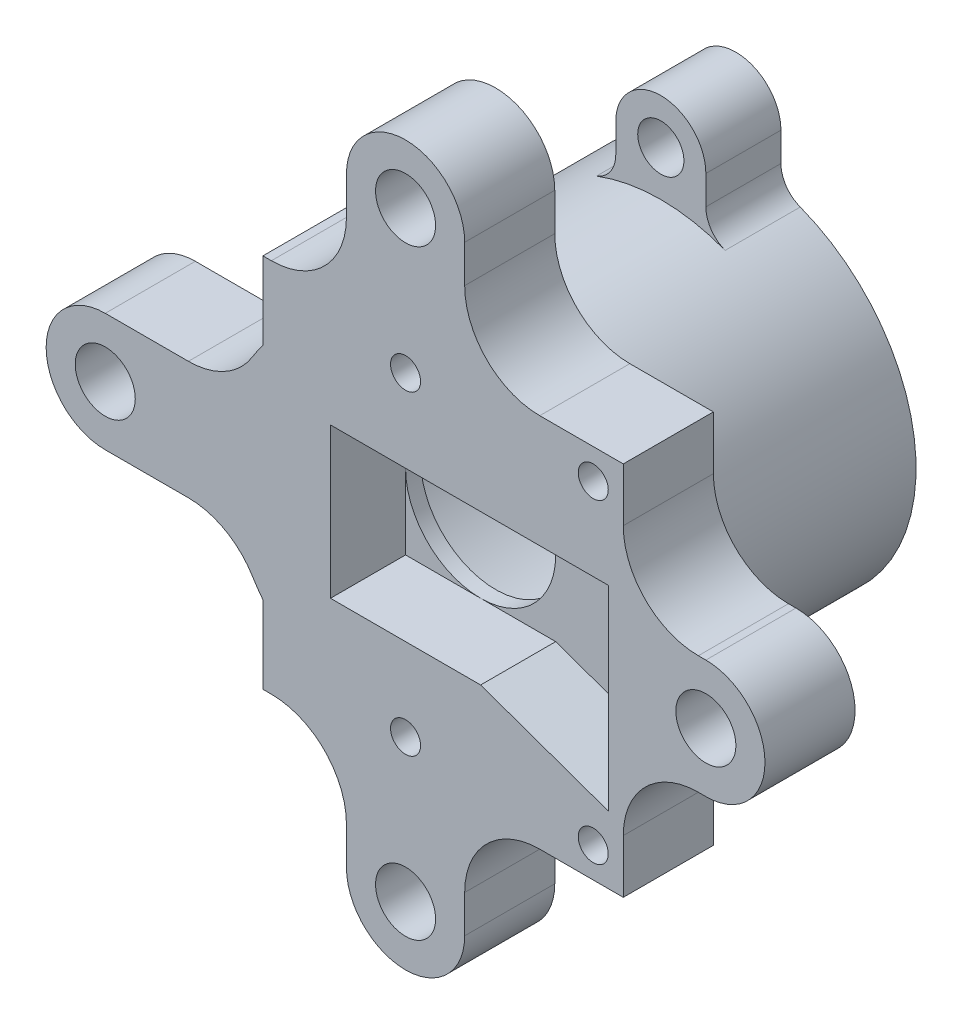
SolidWorks part; units mm, degrees
ref_plane "Front Plane" through (0, 0, 0) normal (1, 0, 0) x (0, 1, 0)
ref_plane "Top Plane" through (0, 0, 0) normal (0, 0, 1) x (0, 1, 0)
ref_plane "Right Plane" through (0, 0, 0) normal (0, 1, 0) x (-1, 0, 0)
sketch "Sketch1" plane through (0, 0, 0) normal (0, 0, 1) x (0, 1, 0)
  circle A0 centre (0, 0) radius 4.75
  circle A2 centre (0, 0) radius 12
extrude "Boss-Extrude1" add sketch "Sketch1" against normal blind 2 contours A2 | A2 A0 | A2 | A2 | A2 | A2 region at (0, -11.6606, 0)
sketch "Sketch2" plane through (0, 0, -2) normal (0, 0, -1) x (1, 0, 0)
  circle A0 centre (0, 0) radius 12
  circle A1 centre (0, 0) radius 10.8716
extrude "Boss-Extrude3" add sketch "Sketch2" along normal blind 20
sketch "Sketch3" plane through (0, 0, -22) normal (0, 0, -1) x (1, 0, 0)
  line L0 (0, 0) -> (0, 15)
  line L1 (-3, 15) -> (-3, 11.619)
  line L2 (3, 15) -> (3, 11.619)
  line L3 (0, 0) -> (3, 0)
  line L4 (-3, -15) -> (-3, -11.619)
  line L5 (3, -15) -> (3, -11.619)
  circle A0 centre (0, 0) radius 12
  circle A1 centre (0, 15) radius 3
  circle A2 centre (0, 15) radius 1.5391
  circle A3 centre (0, -15) radius 3
  circle A4 centre (0, -15) radius 1.5391
  circle M7 centre (0, 0) radius 12
extrude "Boss-Extrude4" add sketch "Sketch3" against normal blind 5 contours A1 L1 M7 | A1 L2 M7 | A2 A1 | L4 A3 M7 | A0 A3 L5 | A3 A4 region at (2.3172, -12.5416, -22) region at (-2.3172, -12.5416, -22) region at (-2.0613, -12.9387, -22) region at (-2.3172, 12.5416, -22) region at (2.3172, 12.5416, -22) region at (-2.0613, 12.9387, -22)
sketch "Sketch5" plane through (0, 0, 0) normal (0, 0, 1) x (1, 0, 0)
  line L0 (0, 0) -> (14.5, 0)
  line L1 (0, 0) -> (0, 10.5)
  line L2 (14.5, 0) -> (-9.5, 0)
  line L3 (14.5, -12.5) -> (14.5, 12.5)
  line L4 (14.5, 12.5) -> (-9.5, 12.5)
  line L5 (-9.5, -12.5) -> (-9.5, 12.5)
  line L6 (0, 10.5) -> (12.5, 10.5)
  line L7 (14.5, -12.5) -> (-9.5, -12.5)
  line L8 (13.5, -5) -> (13.5, -8.0225)
  line L9 (-5, -5) -> (5, -5)
  line L10 (-5, -5) -> (-5, 5)
  line L11 (-5, 5) -> (5, 5)
  line L12 (5, -5) -> (5, 5)
  line L13 (-5, -5) -> (5, 5) construction
  line L14 (-5, 5) -> (5, -5) construction
  line L15 (5, 5) -> (13.5, 5)
  line L16 (5, 5) -> (5, -5)
  line L17 (5, -5) -> (13.5, -5)
  line L18 (13.5, 5) -> (13.5, -5)
  line L19 (13.5, -8.0225) -> (5, -5)
  circle A0 centre (0, 10.5) radius 1
  circle A1 centre (12.5, 10.5) radius 1
  circle A2 centre (0, -10.5) radius 1
  circle A3 centre (12.5, -10.5) radius 1
  circle A4 centre (0, 0) radius 12
  circle M12 centre (0, 0) radius 4.75
  circle M13 centre (0, 0) radius 12
  dimension "D4" = 10
  dimension "D1" = 14.5
  dimension "D2" = 24
  dimension "D3" = 12.5
  dimension "D5" = 10
  dimension "D6" = 8.5
extrude "Boss-Extrude5" add sketch "Sketch5" against normal blind 5 contours A0 L1 L11 L15 L6 M13 | A1 L15 L18 L2 L3 L4 L5 M13 | A0 L6 L5 L2 L10 L11 L1 M13 | L19 L9 L10 L2 L5 A2 M13 | L8 L19 L5 L7 L3 L2 L18 A3 M13 | L5 M13 region at (-4.6617, 6.5575, 0) region at (4.6373, 7.4557, 0) region at (-1.5594, -6.9537, 0) region at (-10.5095, 0, 0) region at (13.7706, 2.5, 0) region at (14, -0.2706, 0)
extrude "Cut-Extrude4" cut sketch "Sketch5<4>" against normal blind 5 contours L11 L10 L2 L1 M12 | L0 L12 L11 L1 M12 | L9 L12 L0 L2 L10 M12 | L6 A0 L1 | L1 A0 L6 | A2 | L12 L17 L2 M13 | L15 L12 L2 M13 | L19 L17 M13 region at (3.6783, 3.6783, 0) region at (4.875, -0.1118, 0) region at (-3.6783, 3.6783, 0) region at (8.3294, 2.4322, 0) region at (8.3294, -2.4322, 0) region at (8.6297, -5.5866, 0) region at (-0.1415, 10.6415, 0) region at (0.4244, 10.0756, 0) region at (0, -10.5, 0)
sketch "Sketch5<4>" plane through (0, 0, 0) normal (0, 0, 1) x (1, 0, 0) same geometry as "Sketch5"
sketch "Sketch6" plane through (0, 0, -5) normal (0, 0, -1) x (1, 0, 0)
  line L0 (14.5, 12.5) -> (14.5, -12.5) construction
  line L1 (-9.5, 12.5) -> (14.5, 12.5)
  line L2 (-9.5, 12.5) -> (-9.5, -12.5)
  line L3 (-9.5, -12.5) -> (14.5, -12.5)
  line L4 (14.5, 12.5) -> (14.5, -12.5)
  circle A0 centre (0, 0) radius 12
  circle M1 centre (12.5, 10.5) radius 1
  circle M2 centre (12.5, -10.5) radius 1
  arc M3 (-9.5, 7.3314) -> (9.9215, 6.75) centre (0, 0) cw
  line M4 (9.9215, 6.75) -> (13.5, 8.0225)
  line M5 (13.5, 8.0225) -> (13.5, -5)
  line M6 (13.5, -5) -> (10.9087, -5)
  arc M7 (10.9087, -5) -> (-9.5, -7.3314) centre (0, 0) cw
  line M8 (-9.5, -7.3314) -> (-9.5, -12.5)
  line M9 (-9.5, -12.5) -> (14.5, -12.5)
  line M10 (14.5, -12.5) -> (14.5, 12.5)
  line M11 (14.5, 12.5) -> (-9.5, 12.5)
  line M12 (-9.5, 12.5) -> (-9.5, 7.3314)
extrude "Boss-Extrude11" add sketch "Sketch6" along normal blind 1 contours M12 M3 M4 M5 M6 M7 M8 M9 M10 M11 M2 M1 | A0 M6 M5 M4 | M1 | M2 region at (2.5, -12.1534, -5) region at (12.404, -1.8318, -5) region at (12.5, -10.5, -5) region at (12.5, 10.5, -5)
combine bodies "Combine1" operation type add bodies to combine 105 108 111
fillet "Fillet2" radius 2 4 edges at (3, 11.619, -19.5) (3, -11.619, -19.5) (-3, 11.619, -19.5) (-3, -11.619, -19.5)
sketch "Sketch7" plane through (0, 0, -5) normal (0, 0, -1) x (1, 0, 0)
  circle A0 centre (0, 0) radius 5
  circle A1 centre (0, 0) radius 12
  arc M1 (0.9438, -10.8306) -> (9.6536, -5) centre (0, 0) ccw
  line M2 (9.6536, -5) -> (-5, -5)
  line M3 (-5, -5) -> (-5, 5)
  line M4 (-5, 5) -> (5, 5)
  line M5 (5, 5) -> (8.8187, 6.3579)
  arc M6 (8.8187, 6.3579) -> (0.9438, 10.8306) centre (0, 0) ccw
  arc M7 (0.9438, 10.8306) -> (-0.9438, 10.8306) centre (0, 10.5) cw
  arc M8 (-0.9438, 10.8306) -> (-0.9438, -10.8306) centre (0, 0) ccw
  arc M9 (-0.9438, -10.8306) -> (0.9438, -10.8306) centre (0, -10.5) cw
extrude "Boss-Extrude13" add sketch "Sketch7" along normal blind 1 contours M9 M1 M2 M3 M4 M5 M6 M7 M8 | A1 A0 M2 M1 M9 M8 M7 M6 M5 M4 | A0 M4 M3 | A0 M3 M2 region at (-3.8832, -3.8832, -5) region at (-2.5, -5.2984, -5) region at (-3.8832, 3.8832, -5) region at (-11.6606, 0, -5)
sketch "Sketch17" plane through (0, 0, 0) normal (0, 0, 1) x (1, 0, 0)
  line L0 (0, 0) -> (0, 20)
  line L1 (-5, 5) -> (13.5, 5) construction
  line L2 (-3.937, 20) -> (3.937, 20)
  line L3 (-3.937, 20) -> (-3.937, 5)
  line L4 (-3.937, 5) -> (3.937, 5)
  line L5 (3.937, 20) -> (3.937, 5)
  line L6 (20, -3.937) -> (5, -3.937)
  line L7 (20, 3.937) -> (5, 3.937)
  line L8 (-3.937, -20) -> (-3.937, -5)
  line L9 (3.937, -20) -> (3.937, -5)
  line L10 (-20, 3.937) -> (-5, 3.937)
  line L11 (-20, -3.937) -> (-5, -3.937)
  circle A0 centre (0, 20) radius 3.937
  circle A1 centre (0, 20) radius 2
  circle A2 centre (20, 0) radius 3.937
  circle A3 centre (20, 0) radius 2
  circle A4 centre (0, -20) radius 3.937
  circle A5 centre (0, -20) radius 2
  circle A6 centre (-20, 0) radius 3.937
  circle A7 centre (-20, 0) radius 2
  circle A8 centre (0, 10.5) radius 1
  circle A9 centre (0, -10.5) radius 1
  point P35 (0, 0)
  arc M8 (-9.5, 7.3314) -> (-9.5, -7.3314) centre (0, 0) ccw
  line M10 (-9.5, -12.5) -> (14.5, -12.5)
  line M11 (14.5, -12.5) -> (14.5, 12.5)
  line M12 (14.5, 12.5) -> (-9.5, 12.5)
  dimension "D2" = 4
  dimension "D1" = 20
extrude "Boss-Extrude14" add sketch "Sketch17" against normal up to surface (6 mm away) contours A6 L11 L10 M8 | A6 A7 | A4 L9 L8 M10 | A4 A5 | A1 L2 A0 L0 | A1 L2 A0 | A1 L0 A0 L2 | A0 L3 L0 M12 | A0 L0 L5 M12 | A2 L7 L6 M11 | A2 A3 region at (0, -14.7915, 0) region at (15.8643, 0, 0) region at (-2.1773, 14.7915, 0) region at (2.1773, 14.7915, 0) region at (0, 23.849, 0) region at (-1.9569, 18.0431, 0) region at (1.9569, 18.0431, 0) region at (22.7051, 2.7051, 0) region at (0, -23.8256, 0) region at (-14.416, 0, 0) region at (-17.2949, 2.7051, 0) up to face at (2.0833, 0, -6)
fillet "Fillet3" radius 5 8 edges at (3.937, -12.5, -3) (14.5, -3.937, -3) (14.5, 3.937, -3) (3.937, 12.5, -3) (-3.937, 12.5, -3) (-11.3358, 3.937, -3) (-11.3358, -3.937, -3) (-3.937, -12.5, -3)
sketch "Sketch8" plane through (0, 0, 0) normal (0, 0, 1) x (1, 0, 0)
  line L0 (0, 0) -> (14.1421, 14.1421)
  line L1 (-14.1421, 14.1421) -> (-17.6777, 10.6066)
  line L2 (-9.5, 12.5) -> (14.5, 12.5)
  line L3 (-9.5, 12.5) -> (-9.5, -12.5)
  line L4 (-9.5, -12.5) -> (14.5, -12.5)
  line L5 (14.5, 12.5) -> (14.5, -12.5)
  line L6 (-17.6777, 10.6066) -> (-9.5, 2.0744)
  line L7 (-14.1421, 14.1421) -> (-10.6066, 17.6777)
  line L8 (-10.6066, 17.6777) -> (-5.4289, 12.5)
  line L9 (-9.5, 0) -> (-14.1421, 0)
  line L10 (-10.6066, -17.6777) -> (-5.4289, -12.5)
  line L11 (-17.6777, -10.6066) -> (-9.5, -2.0744)
  line L12 (10.6066, 17.6777) -> (2.0744, 9.5)
  line L13 (17.6777, 10.6066) -> (12.5, 5.4289)
  line L14 (17.6777, -10.6066) -> (9.5, -2.0744)
  line L15 (10.6066, -17.6777) -> (5.4289, -12.5)
  line L16 (-10.6066, -17.6777) -> (-2.0744, -9.5)
  line L17 (-17.6777, -10.6066) -> (-12.5, -5.4289)
  circle A0 centre (14.1421, 14.1421) radius 5
  circle A1 centre (14.1421, 14.1421) radius 1.5
  circle A2 centre (14.1421, -14.1421) radius 1.5
  circle A3 centre (14.1421, -14.1421) radius 5
  circle A4 centre (-14.1421, -14.1421) radius 1.5
  circle A5 centre (-14.1421, -14.1421) radius 5
  circle A6 centre (-14.1421, 14.1421) radius 1.5
  circle A7 centre (-14.1421, 14.1421) radius 5
  point P23 (0, 0)
  point P46 (0, 0)
  dimension "D1" = 4
  dimension "D3" = 3
  dimension "D2" = 4
sketch "Sketch15" plane through (3, 0, 0) normal (1, 0, 0) x (0, 1, 0)
  line L3 (-11.5, -17) -> (11.5, -17)
  line L4 (0, -19.5) -> (0, -17.3262)
  line L5 (-11.5, -17) -> (-11.5, -22)
  line L6 (-11.5, -22) -> (11.5, -22)
  line L7 (11.5, -17) -> (11.5, -22)
  circle A0 centre (-11.5, -19.5) radius 1.25
  circle A2 centre (-11.5, -19.5) radius 2.5
  circle A3 centre (11.5, -19.5) radius 1.25
  circle A4 centre (11.5, -19.5) radius 2.5
  dimension "D2" = 2.5
  dimension "D1" = 11.5
sketch "Sketch16" plane through (0, 0, -22) normal (0, 0, -1) x (1, 0, 0)
  circle A0 centre (0, 0) radius 10.8716
